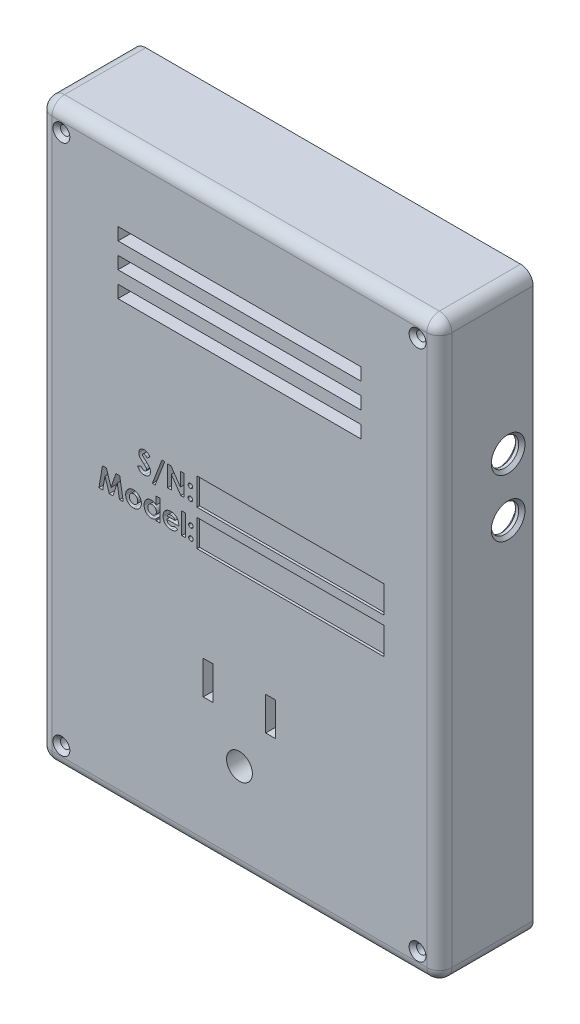
SolidWorks part; units mm, degrees
ref_plane "Front Plane" through (0, 0, 0) normal (0, 0, 1) x (1, 0, 0)
ref_plane "Top Plane" through (0, 0, 0) normal (0, 1, 0) x (1, 0, 0)
ref_plane "Right Plane" through (0, 0, 0) normal (1, 0, 0) x (0, 0, -1)
sketch "Sketch4" plane through (0, 0, 0) normal (0, 0, 1) x (1, 0, 0)
  line L1 (-36.195, 56.515) -> (36.195, 56.515)
  line L2 (-38.735, 53.975) -> (-38.735, -53.975)
  line L3 (-36.195, -56.515) -> (36.195, -56.515)
  line L4 (38.735, 53.975) -> (38.735, -53.975)
  arc A0 (-38.735, 53.975) -> (-36.195, 56.515) centre (-36.195, 53.975) ccw
  arc A1 (36.195, 56.515) -> (38.735, 53.975) centre (36.195, 53.975) ccw
  arc A2 (-36.195, -56.515) -> (-38.735, -53.975) centre (-36.195, -53.975) ccw
  arc A3 (38.735, -53.975) -> (36.195, -56.515) centre (36.195, -53.975) ccw
  dimension "D1" = 5.08
sketch "Sketch5" plane through (0, 0, 0) normal (0, 0, 1) x (1, 0, 0)
  line L0 (-40.64, -58.42) -> (40.64, -58.42)
  line L1 (-40.64, 58.42) -> (40.64, 58.42)
  line L2 (-40.64, 58.42) -> (-40.64, -58.42)
  line L3 (-40.64, -58.42) -> (40.64, -58.42) construction
  line L4 (40.64, 58.42) -> (40.64, -58.42)
  line L5 (-40.64, 58.42) -> (40.64, -58.42) construction
  line L6 (-40.64, -58.42) -> (40.64, 58.42) construction
  line L7 (-40.64, 58.42) -> (40.64, 58.42) construction
  line L9 (-40.64, 0) -> (40.64, 0) construction
  point P0 (0, 0)
sketch "Sketch8" plane through (0, 0, 0) normal (0, 0, 1) x (1, 0, 0)
  circle A0 centre (-36.195, 53.975) radius 0.9525
  circle A1 centre (-36.195, -53.975) radius 0.9525
  circle A2 centre (36.195, 53.975) radius 0.9525
  circle A3 centre (36.195, -53.975) radius 0.9525
  dimension "D1" = 1.905
extrude "Case" add sketch "Sketch5" along normal blind 12.7
extrude "Case Cut" cut sketch "Sketch4" along normal blind 7.366
ref_plane "Inside Back Plane" through (0, 0, 7.366) normal (0, 0, -1) x (-1, 0, 0)
sketch "Sketch11" plane through (0, 0, 7.366) normal (0, 0, -1) x (-1, 0, 0)
  circle A0 centre (-35.56, 48.641) radius 0.8255
  circle A1 centre (35.56, 48.641) radius 0.8255
  circle A2 centre (35.56, -48.641) radius 0.8255
  circle A3 centre (-35.56, -48.641) radius 0.8255
  dimension "D1" = 1.651
sketch "Sketch13" plane through (0, 0, 7.366) normal (0, 0, -1) x (-1, 0, 0)
  line L0 (-36.195, 51.435) -> (36.195, 51.435) construction
  line L1 (-36.195, -51.435) -> (36.195, -51.435) construction
  circle A0 centre (-35.56, 48.641) radius 2.159
  circle A1 centre (35.56, 48.641) radius 2.159
  circle A2 centre (-35.56, -48.641) radius 2.159
  circle A3 centre (35.56, -48.641) radius 2.159
  dimension "D1" = 4.318
  dimension "D2" = 2.794
  dimension "D5" = 2.794
extrude "Board Mount" add sketch "Sketch13" along normal blind 2.54
extrude "Board Mount Screw Cut" cut sketch "Sketch11" along normal blind 5.588
extrude "FacePlate Screw Cut" cut sketch "Sketch8" along normal through all
sketch "Sketch14" plane through (0, 0, 7.366) normal (0, 0, -1) x (-1, 0, 0)
  line L0 (7.366, -27.559) -> (38.735, -27.559) construction
  line L1 (-7.366, -24.1554) -> (-5.334, -24.1554)
  line L2 (-7.366, -24.1554) -> (-7.366, -30.9626)
  line L3 (-7.366, -30.9626) -> (-5.334, -30.9626)
  line L4 (-5.334, -24.1554) -> (-5.334, -30.9626)
  line L5 (5.334, -24.1554) -> (7.366, -24.1554)
  line L6 (5.334, -24.1554) -> (5.334, -30.9626)
  line L7 (5.334, -30.9626) -> (7.366, -30.9626)
  line L8 (7.366, -24.1554) -> (7.366, -30.9626)
  line L10 (-7.366, -27.559) -> (-38.735, -27.559) construction
  line L13 (-36.195, -51.435) -> (36.195, -51.435) construction
  line L14 (-6.35, -24.1554) -> (-6.35, -30.9626) construction
  line L15 (6.35, -24.1554) -> (6.35, -30.9626) construction
  circle A0 centre (0, -39.497) radius 2.6289
  dimension "D4" = 5.2578
  dimension "D6" = 11.938
  dimension "D1" = 2.032
  dimension "D2" = 6.8072
  dimension "D3" = 12.7
  dimension "D5" = 11.938
ref_plane "Left Side Plane" through (40.64, 0, 0) normal (1, 0, 0) x (0, 0, -1)
sketch "Sketch18" plane through (40.64, 0, 0) normal (1, 0, 0) x (0, 0, -1)
  line L0 (-9.017, 51.689) -> (0, 51.689) construction
  line L4 (-9.017, 50.5841) -> (0, 50.5841) construction
  line L5 (0, 42.672) -> (0, 50.5841) construction
  line L6 (-9.017, 37.1395) -> (0, 37.1395) construction
  circle A1 centre (1.27, 28.829) radius 2.794
  circle A2 centre (1.27, 17.145) radius 2.794
  dimension "D2" = 5.588
  dimension "D3" = 22.86
  dimension "D4" = 11.684
extrude "Outlet Cut" cut sketch "Sketch14" against normal through all
ref_plane "Top Back Plane" through (0, 0, 0) normal (0, 0, -1) x (-1, 0, 0)
sketch "Sketch24" plane through (0, 0, 0) normal (0, 0, 1) x (1, 0, 0)
  line L0 (-40.64, -58.42) -> (40.64, -58.42)
  line L1 (-40.64, 58.42) -> (40.64, 58.42)
  line L2 (-40.64, 58.42) -> (-40.64, -58.42)
  line L3 (-40.64, -58.42) -> (40.64, -58.42) construction
  line L4 (40.64, 58.42) -> (40.64, -58.42)
  line L5 (-40.64, 58.42) -> (40.64, -58.42) construction
  line L6 (-40.64, -58.42) -> (40.64, 58.42) construction
  line L7 (-40.64, 58.42) -> (40.64, 58.42) construction
  line L9 (-40.64, 0) -> (40.64, 0) construction
  point P0 (0, 0)
extrude "Boss-Extrude1" add sketch "Sketch24" against normal blind 6.35
sketch "Sketch26" plane through (0, 0, 0) normal (0, 0, 1) x (1, 0, 0)
  line L1 (-36.195, 56.515) -> (36.195, 56.515)
  line L2 (-38.735, 53.975) -> (-38.735, -53.975)
  line L3 (-36.195, -56.515) -> (36.195, -56.515)
  line L4 (38.735, 53.975) -> (38.735, -53.975)
  arc A0 (-38.735, 53.975) -> (-36.195, 56.515) centre (-36.195, 53.975) ccw
  arc A1 (36.195, 56.515) -> (38.735, 53.975) centre (36.195, 53.975) ccw
  arc A2 (-36.195, -56.515) -> (-38.735, -53.975) centre (-36.195, -53.975) ccw
  arc A3 (38.735, -53.975) -> (36.195, -56.515) centre (36.195, -53.975) ccw
  dimension "D1" = 5.08
extrude "Cut-Extrude1" cut sketch "Sketch26" against normal blind 6.35
fillet "Fillet11" radius 2.54 1 edges at (40.64, -58.42, 3.175) type face fillet first side face at (40.64, 0, 3.175) second side face at (0, -58.42, 3.175)
fillet "Fillet12" radius 2.54 1 edges at (40.64, 58.42, 3.175) type face fillet first side face at (0, 58.42, 3.175) second side face at (40.64, 1.27, 3.175)
fillet "Fillet13" radius 2.54 1 edges at (-40.64, 58.42, 3.175) type face fillet first side face at (-1.27, 58.42, 3.175) second side face at (-40.64, 0, 3.175)
sketch "Sketch28" plane through (0, 0, 0) normal (0, 0, -1) x (-1, 0, 0)
  circle A0 centre (-36.195, 53.975) radius 0.9525
  circle A1 centre (-36.195, -53.975) radius 0.9525
  circle A2 centre (36.195, 53.975) radius 0.9525
  circle A3 centre (36.195, -53.975) radius 0.9525
  dimension "D1" = 1.905
extrude "Cut-Extrude3" cut sketch "Sketch28" along normal through all
fillet "Fillet14" radius 2.54 1 edges at (-40.64, -58.42, 3.175) type face fillet first side face at (-40.64, -1.27, 3.175) second side face at (-1.27, -58.42, 3.175)
ref_plane "Plane1" through (0, 0, -6.35) normal (0, 0, -1) x (-1, 0, 0)
sketch "Sketch30" plane through (0, 0, -6.35) normal (0, 0, -1) x (-1, 0, 0)
  line L8 (-39.624, -57.404) -> (39.624, -57.404)
  line L10 (39.624, 57.404) -> (39.624, -57.404)
  line L11 (-39.624, 57.404) -> (39.624, 57.404)
  line L12 (-39.624, 57.404) -> (-39.624, -57.404)
  point P0 (0, 0)
extrude "Cut-Extrude4" cut sketch "Sketch30" against normal blind 2.032
fillet "Fillet15" radius 2.54 1 edges at (39.624, 57.404, -5.334) type face fillet first side face at (39.624, 0, -5.334) second side face at (0, 57.404, -5.334)
fillet "Fillet16" radius 2.54 1 edges at (-39.624, 57.404, -5.334) type face fillet first side face at (-39.624, 0, -5.334) second side face at (-1.27, 57.404, -5.334)
fillet "Fillet17" radius 2.54 1 edges at (-39.624, -57.404, -5.334) type face fillet first side face at (-39.624, -1.27, -5.334) second side face at (0, -57.404, -5.334)
fillet "Fillet18" radius 2.54 1 edges at (39.624, -57.404, -5.334) type face fillet first side face at (39.624, -1.27, -5.334) second side face at (1.27, -57.404, -5.334)
ref_plane "Plane2" through (0, 0, 12.7) normal (0, 0, 1) x (1, 0, 0)
extrude "Cut-Extrude5" cut sketch "Sketch18" against normal blind 2.54
chamfer "Chamfer6" distance 0.635 angle 45 4 edges at (40.64, 17.145, -4.064) (40.64, 28.829, -4.064) (38.735, 26.035, -1.27) (38.735, 14.351, -1.27)
fillet "Fillet19" radius 2.54 8 edges at (39.8961, -57.6761, 12.7) (0, -58.42, 12.7) (-39.8961, -57.6761, 12.7) (-40.64, 0, 12.7) (-39.8961, 57.6761, 12.7) (0, 58.42, 12.7) (39.8961, 57.6761, 12.7) (40.64, 0, 12.7)
chamfer "Chamfer7" distance 0.762 angle 45 4 edges at (37.1475, 53.975, 12.7) (-35.2425, 53.975, 12.7) (-35.2425, -53.975, 12.7) (37.1475, -53.975, 12.7)
sketch "Sketch31" plane through (0, 0, 12.7) normal (0, 0, 1) x (1, 0, 0)
  line L1 (-8.6427, 7.3091) -> (29.4287, 7.3091)
  line L2 (-8.6427, 7.3091) -> (-8.6427, 1.7965)
  line L3 (-8.6427, 1.7965) -> (29.4287, 1.7965)
  line L4 (29.4287, 7.3091) -> (29.4287, 1.7965)
  line L5 (-8.6427, 0) -> (29.4287, 0)
  line L6 (-8.6427, 0) -> (-8.6427, -5.5047)
  line L7 (-8.6427, -5.5047) -> (29.4287, -5.5047)
  line L8 (29.4287, 0) -> (29.4287, -5.5047)
extrude "Cut-Extrude6" cut sketch "Sketch31" against normal blind 0.508
sketch "Sketch32" plane through (0, 0, 12.7) normal (0, 0, 1) x (1, 0, 0)
  text T0 "S/N:" font "Century Gothic" height in points 16
  text T1 "Model:" font "Century Gothic" height in points 16
extrude "Cut-Extrude7" cut sketch "Sketch32" against normal blind 1.905
sketch "Sketch33" plane through (0, 0, 12.7) normal (0, 0, 1) x (1, 0, 0)
  line L0 (-24.6942, 41.91) -> (-38.1, 41.91) construction
  line L1 (-24.6942, 43.18) -> (24.6942, 43.18)
  line L2 (-24.6942, 43.18) -> (-24.6942, 40.64)
  line L3 (-24.6942, 40.64) -> (24.6942, 40.64)
  line L4 (24.6942, 43.18) -> (24.6942, 40.64)
  line L5 (-38.1, 55.88) -> (-38.1, -55.88) construction
  line L6 (24.6942, 41.91) -> (38.1, 41.91) construction
  line L7 (38.1, -55.88) -> (38.1, 55.88) construction
  line L8 (0, 40.64) -> (0, 38.1) construction
  line L9 (-24.6942, 38.1) -> (24.6942, 38.1)
  line L10 (-24.6942, 38.1) -> (-24.6942, 35.56)
  line L11 (-24.6942, 35.56) -> (24.6942, 35.56)
  line L12 (24.6942, 38.1) -> (24.6942, 35.56)
  line L13 (0, 35.56) -> (0, 33.02) construction
  line L14 (-24.6942, 33.02) -> (24.6942, 33.02)
  line L15 (-24.6942, 33.02) -> (-24.6942, 30.48)
  line L16 (-24.6942, 30.48) -> (24.6942, 30.48)
  line L17 (24.6942, 33.02) -> (24.6942, 30.48)
  line L18 (0, 43.18) -> (0, 55.88) construction
  line L19 (38.1, 55.88) -> (-38.1, 55.88) construction
  dimension "D1" = 2.54
  dimension "D2" = 2.54
  dimension "D3" = 2.54
  dimension "D4" = 12.7
extrude "Cut-Extrude8" cut sketch "Sketch33" against normal blind 27.94
